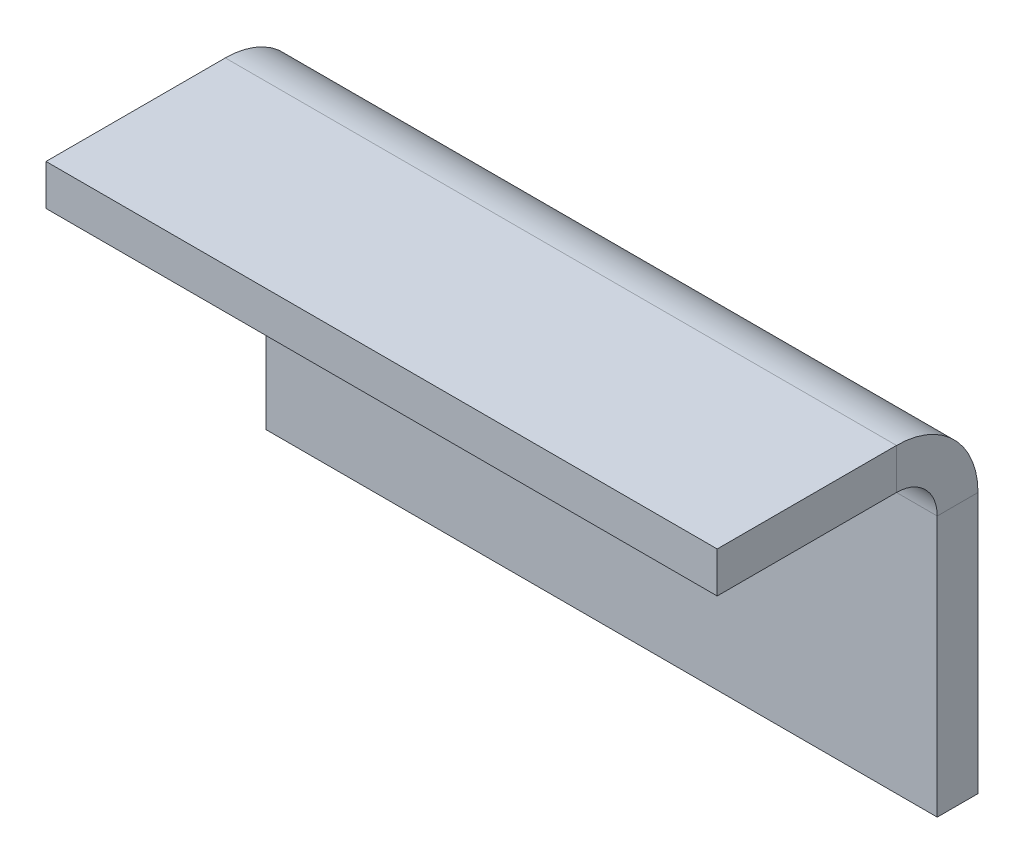
SolidWorks part; units mm, degrees
note: The reader was unsure of these and kept them because the rebuilt part matched: flange length of "Edge-Flange1".
material "6061-T6 (SS)"
ref_plane "X-Y Datum" through (0, 0, 0) normal (0, 0, 1) x (1, 0, 0)
ref_plane "X-Z Datum" through (0, 0, 0) normal (0, 1, 0) x (1, 0, 0)
ref_plane "Y-Z Datum" through (0, 0, 0) normal (1, 0, 0) x (0, 0, -1)
sketch "Sketch2" plane through (0, 0, 0) normal (0, 0, 1) x (1, 0, 0)
  line L1 (0, 0) -> (52.2915, 0)
  line L2 (0, 0) -> (0, 20.32)
  line L3 (0, 20.32) -> (52.2915, 20.32)
  line L4 (52.2915, 0) -> (52.2915, 20.32)
base flange "Base-Flange1" sketch "Sketch2" thickness 3.175 reverse thickness direction no parameters "D1"=3.175
edge flange "Edge-Flange1" sketch "Sketch9" flange angle 90 flange length 20.32 flange position bend outside bend radius 3.175 thickness 3.175 relief rectangular parameters "D6"=10
sketch "Sketch9" plane through (0, 20.32, 0) normal (0, 1, 0) x (-1, 0, 0)
  line L0 (-52.2915, 0) -> (0, 0) construction
  line L1 (-52.2915, 0) -> (0, 0)
  line L2 (-52.2915, 0) -> (-52.2915, 17.145)
  line L3 (-52.2915, 17.145) -> (0, 17.145)
  line L4 (0, 17.145) -> (0, 0)
bend "EdgeBend1" bend radius 3.175 bend angle 90 parameters "D5"=1
sketch "Bend-Lines1" [suppressed] plane through (0, 0, 0) normal (0, 1, 0) x (1, 0, 0)
sketch "Bounding-Box1" [suppressed] plane through (0, 0, 0) normal (0, 1, 0) x (1, 0, 0)
sheet metal parameters "Sheet-Metal1" thickness 3.175 parameters "D1"=3.175
flat pattern "Flat-Pattern1" [suppressed]
sketch "Bend-Lines2" plane through (0, 0, 0) normal (0, 1, 0) x (1, 0, 0)
sketch3d "Bounding-Box2" [suppressed]
  line L0 (0, 0, 0) -> (-52.2915, 0, 0) construction
  line L1 (0, 20.32, 0) -> (-52.2915, 20.32, 0) construction
  line L2 (0, 0, 0) -> (0, 20.32, 0) construction
  line L3 (-52.2915, 0, 0) -> (-52.2915, 20.32, 0) construction
sheet metal parameters "Sheet-Metal2" thickness 3.175 parameters "D1"=3.175
flat pattern "Flat-Pattern1"
sketch "Bend-Lines2" plane through (0, 0, 0) normal (0, 0, 1) x (1, 0, 0)
  line L0 (52.2915, 24.0605) -> (0, 24.0605) construction
  line L1 (52.2915, 24.0605) -> (0, 24.0605) construction
sketch3d "Bounding-Box2" [suppressed]
  line L0 (0, 0, 0) -> (52.2915, 0, 0) construction
  line L1 (0, 41.7709, 0) -> (52.2915, 41.7709, 0) construction
  line L2 (0, 0, 0) -> (0, 41.7709, 0) construction
  line L3 (52.2915, 0, 0) -> (52.2915, 41.7709, 0) construction
bend of the flat pattern "Flatten-<EdgeBend1>1"
